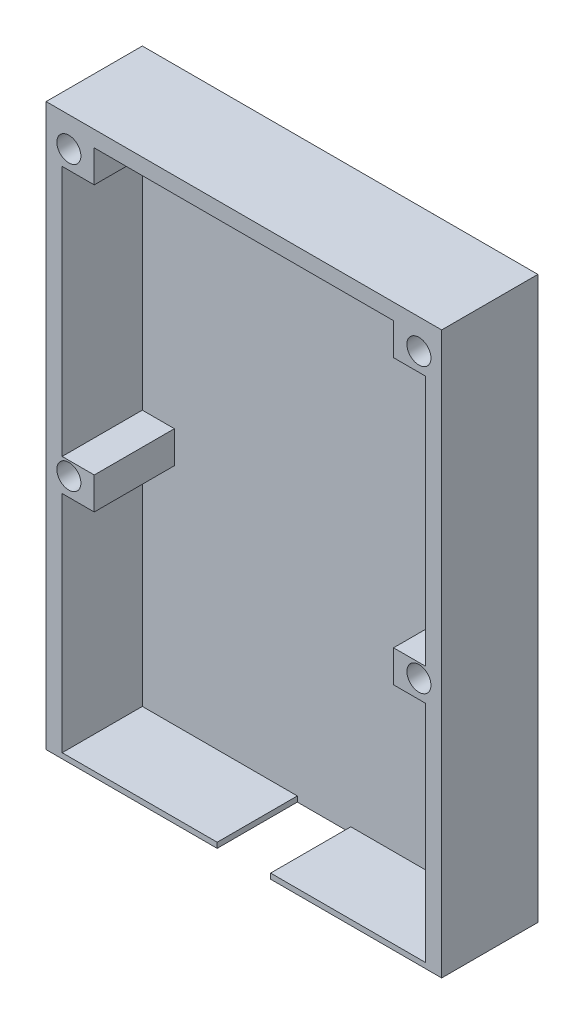
SolidWorks part; units mm, degrees
ref_plane "Plan de face" through (0, 0, 0) normal (0, 0, 1) x (1, 0, 0)
ref_plane "Plan de dessus" through (0, 0, 0) normal (0, 1, 0) x (1, 0, 0)
ref_plane "Plan de droite" through (0, 0, 0) normal (1, 0, 0) x (0, 0, -1)
sketch "Esquisse1" plane through (0, 0, 0) normal (0, 0, 1) x (1, 0, 0)
  line L1 (-37, -52.5) -> (37, -52.5)
  line L2 (-37, -52.5) -> (-37, 52.5)
  line L3 (-37, 52.5) -> (37, 52.5)
  line L4 (37, -52.5) -> (37, 52.5)
  line L5 (-37, -52.5) -> (37, 52.5) construction
  line L6 (-37, 52.5) -> (37, -52.5) construction
  point P0 (0, 0)
  dimension "D1" = 105
  dimension "D2" = 74
extrude "Boss.-Extru.1" add sketch "Esquisse1" along normal blind 18
sketch "Esquisse2" plane through (0, 0, 18) normal (0, 0, 1) x (1, 0, 0)
  line L8 (-34, 49.5) -> (-34, -49.5)
  line L9 (-34, -49.5) -> (34, -49.5)
  line L10 (34, -49.5) -> (34, 49.5)
  line L11 (34, 49.5) -> (-34, 49.5)
  line L12 (-34, 49.5) -> (-34, -49.5)
  line L13 (-34, -49.5) -> (34, -49.5)
  line L14 (34, -49.5) -> (34, 49.5)
  line L15 (34, 49.5) -> (-34, 49.5)
  dimension "D1" = 3
extrude "Enlèv. mat.-Extru.1" cut sketch "Esquisse2" against normal blind 15
sketch "Esquisse3" plane through (0, 0, 18) normal (0, 0, 1) x (1, 0, 0)
  line L0 (-34, 49.5) -> (-28, 49.5)
  line L1 (-34, 49.5) -> (-34, 43.5)
  line L2 (-28, 49.5) -> (-28, 43.5)
  line L3 (-34, 43.5) -> (-28, 43.5)
  line L4 (34, 49.5) -> (-34, 49.5) construction
  dimension "D1" = 6
  dimension "D2" = 6
extrude "Boss.-Extru.2" add sketch "Esquisse3" against normal up to surface (15 mm away) up to face at (0, 0, 3)
hole_wizard "Dégagement M41" positions "Esquisse5" profile "Esquisse6" hole size "M4" standard "JIS" end condition through all
sketch "Esquisse5" plane through (0, 0, 18) normal (0, 0, 1) x (1, 0, 0)
  point P0 (-32.7451, 46.9268)
sketch "Esquisse6" plane through (-32.7451, 46.9268, 18) normal (1, 0, 0) x (0, -1, 0)
  line L0 (0, 0) -> (0, 18)
  line L1 (0, 18) -> (2.25, 18)
  line L2 (2.25, 18) -> (2.25, 0)
  line L5 (2.25, 0) -> (0, 0)
  line L11 (0, -6.35) -> (0, 107.95) construction
  dimension "Diamètre du perçage jusqu'au prochain" = 4.5
  dimension "Profondeur du perçage jusqu'au prochain" = 18
ref_point "Point1"
ref_axis "Axe1" through (0, 52.5, 9) along (0, 1, 0)
ref_plane "Plan1" through (0, 0, 0) normal (1, 0, 0) x (0, 1, 0)
ref_point "Point2"
ref_axis "Axe2" through (-37, 0, 9) along (-1, 0, 0)
ref_plane "Plan2" through (0, 0, 0) normal (0, -1, 0) x (-1, 0, 0)
sketch "Esquisse7" plane through (0, -52.5, 0) normal (0, -1, 0) x (1, 0, 0)
  line L0 (-37, 18) -> (37, 18) construction
  line L1 (-5, 33) -> (5, 33)
  line L2 (-5, 33) -> (-5, 3)
  line L3 (-5, 3) -> (5, 3)
  line L4 (5, 33) -> (5, 3)
  line L5 (-5, 33) -> (5, 3) construction
  line L6 (-5, 3) -> (5, 33) construction
  line L8 (-34, 3) -> (34, 3) construction
  point P0 (0, 18)
  dimension "D1" = 10
extrude "Enlèv. mat.-Extru.2" cut sketch "Esquisse7" against normal blind 15
mirror "Symétrie5" about plane through (0, 0, 0) normal (1, 0, 0) of "Boss.-Extru.2", "Dégagement M41"
pattern_linear "Répétition linéaire3" count 2 spacing 53 along (0, -1, 0) of "Symétrie5"
sketch "Esquisse8" plane through (0, -49.5, 0) normal (0, 1, 0) x (1, 0, 0)
  line L0 (34, -3) -> (-34, -3)
  line L1 (34, -3) -> (34, -36.5303)
  line L2 (-34, -3) -> (-34, -36.5303)
  line L3 (34, -36.5303) -> (-34, -36.5303)
extrude "Enlèv. mat.-Extru.3" cut sketch "Esquisse8" against normal blind 2
